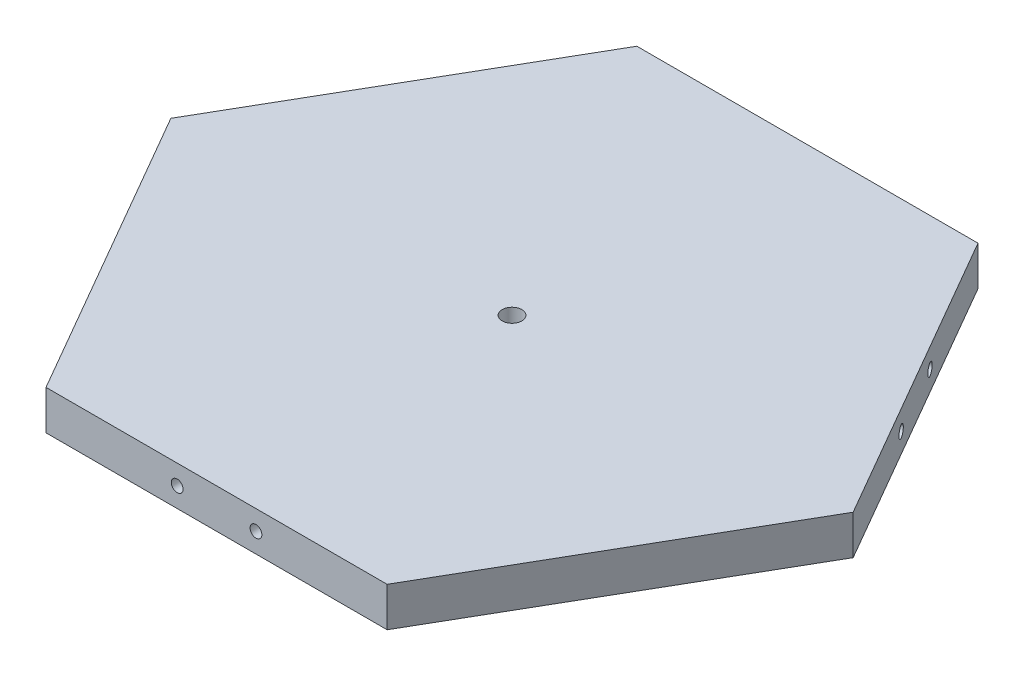
SolidWorks part; units mm, degrees
ref_plane "Front Plane" through (0, 0, 0) normal (0, 0, 1) x (1, 0, 0)
ref_plane "Top Plane" through (0, 0, 0) normal (0, 1, 0) x (1, 0, 0)
ref_plane "Right Plane" through (0, 0, 0) normal (1, 0, 0) x (0, 0, -1)
sketch "Sketch1" plane through (0, 0, 0) normal (0, 1, 0) x (1, 0, 0)
  line L1 (86.6025, 0) -> (43.3013, 75)
  line L2 (43.3013, 75) -> (-43.3013, 75)
  line L3 (-43.3013, 75) -> (-86.6025, 0)
  line L4 (-86.6025, 0) -> (-43.3013, -75)
  line L5 (-43.3013, -75) -> (43.3013, -75)
  line L6 (43.3013, -75) -> (86.6025, 0)
  circle A0 centre (0, 0) radius 75 construction
  dimension "D1" = 150
extrude "Boss-Extrude1" add sketch "Sketch1" along normal blind 10
sketch "Sketch2" plane through (0, 0, 75) normal (0, 0, 1) x (1, 0, 0)
  line L0 (-43.3013, 0) -> (43.3013, 0) construction
  line L1 (-43.3013, 10) -> (-43.3013, 0) construction
  circle A0 centre (-10, 5) radius 1.5
  circle A1 centre (10, 5) radius 1.5
  dimension "D1" = 3
  dimension "D2" = 10
  dimension "D3" = 10
  dimension "D4" = 5
extrude "Cut-Extrude1" cut sketch "Sketch2" against normal blind 10
sketch "Sketch3" plane through (0, 10, 0) normal (0, 1, 0) x (1, 0, 0)
  circle A0 centre (0, 0) radius 2.5
  dimension "D1" = 5
extrude "Cut-Extrude2" cut sketch "Sketch3" against normal blind 10
pattern_circular "CirPattern1" count 3 over 360 about axis through (0, 0, 0) along (0, 1, 0) of "Cut-Extrude1" reverse direction yes
sketch "Sketch4" plane through (0, 10, 0) normal (0, 1, 0) x (1, 0, 0)
  line L0 (0, 0) -> (86.6025, 0) construction
  line L1 (0, 0) -> (64.9519, 37.5) construction
  line L2 (86.6025, 0) -> (43.3013, 75) construction
  line L3 (0, 0) -> (-64.9519, 37.5) construction
  line L4 (-43.3013, 75) -> (-86.6025, 0) construction
  line L5 (0, 0) -> (0, -75) construction
  line L6 (-43.3013, -75) -> (43.3013, -75) construction
  line L7 (64.9519, 37.5) -> (59.9519, 46.1603) construction
  line L8 (64.9519, 37.5) -> (69.9519, 28.8397) construction
  line L9 (-64.9519, 37.5) -> (-69.9519, 28.8397) construction
  line L10 (-64.9519, 37.5) -> (-59.9519, 46.1603) construction
  line L11 (0, -75) -> (-10, -75) construction
  line L12 (0, -75) -> (10, -75) construction
  line L13 (-69.9519, 28.8397) -> (0, 0)
  line L14 (0, 0) -> (-59.9519, 46.1603)
  line L15 (0, 0) -> (59.9519, 46.1603)
  line L16 (0, 0) -> (69.9519, 28.8397)
  line L17 (0, 0) -> (-10, -75)
  line L18 (0, 0) -> (10, -75)
  dimension "D1" = 10
  dimension "D2" = 10
  dimension "D3" = 10
  dimension "D4" = 10
  dimension "D5" = 10
  dimension "D6" = 10
  dimension "D7" = 22.405
  dimension "D8" = 37.595
  dimension "D9" = 142.405
  dimension "D10" = 157.595
  dimension "D11" = 262.405
  dimension "D12" = 277.595
